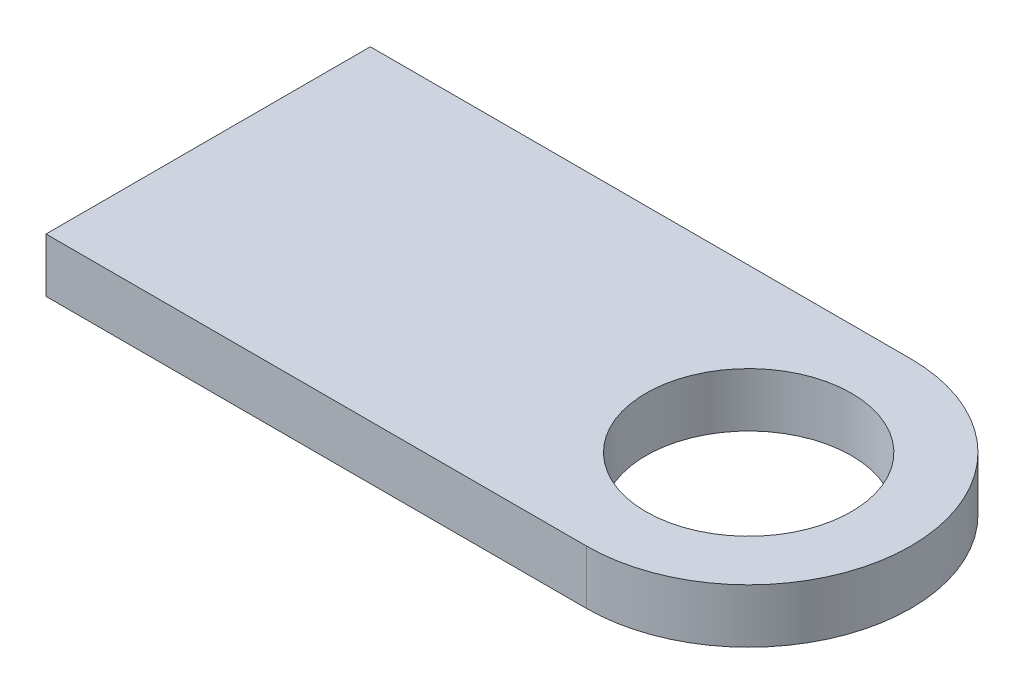
SolidWorks part; units mm, degrees
ref_plane "Front Plane" through (0, 0, 0) normal (0, 0, 1) x (1, 0, 0)
ref_plane "Top Plane" through (0, 0, 0) normal (0, 1, 0) x (1, 0, 0)
ref_plane "Right Plane" through (0, 0, 0) normal (1, 0, 0) x (0, 0, -1)
sketch "Sketch1" plane through (0, 0, 0) normal (0, 1, 0) x (1, 0, 0)
  line L1 (0, 15) -> (-50, 15)
  line L2 (0, 15) -> (0, -15)
  line L3 (0, -15) -> (-50, -15)
  line L4 (-50, 15) -> (-50, -15)
  circle A0 centre (0, 0) radius 9.5
  circle A1 centre (0, 0) radius 15
  dimension "D1" = 19
  dimension "D2" = 30
  dimension "D3" = 30
  dimension "D4" = 50
extrude "Boss-Extrude1" add sketch "Sketch1" along normal blind 5 contours A1 L1 L4 L3 | L2 A1 A0 | L2 A1 A0 region at (-30.7438, 0, 0) region at (10.3694, 0, -10.3694) region at (-0.3354, 0, -12.25)
